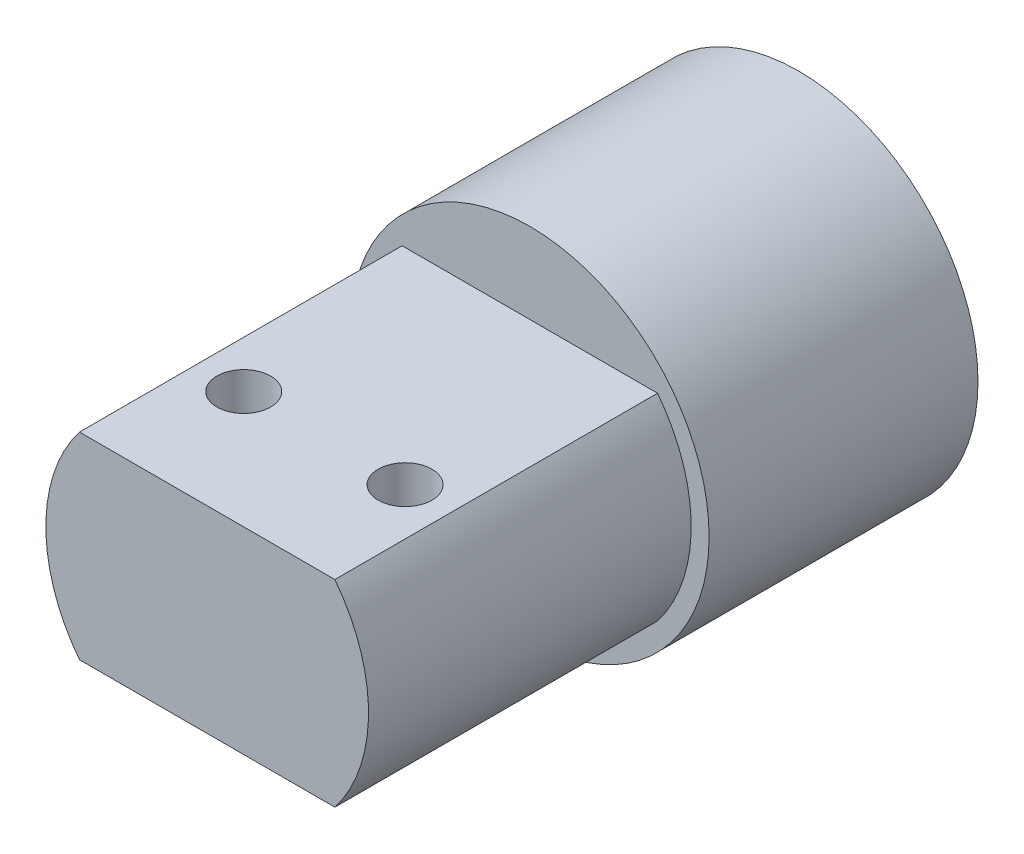
SolidWorks part; units mm, degrees
ref_plane "前视基准面" through (0, 0, 0) normal (0, 0, 1) x (1, 0, 0)
ref_plane "上视基准面" through (0, 0, 0) normal (0, 1, 0) x (1, 0, 0)
ref_plane "右视基准面" through (0, 0, 0) normal (1, 0, 0) x (0, 0, -1)
sketch "草图1" plane through (0, 0, 0) normal (0, 0, 1) x (1, 0, 0)
  line L0 (-11.4891, -8) -> (11.4891, -8)
  arc A0 (11.4891, -8) -> (-11.4891, -8) centre (0, 0) ccw
  circle A1 centre (0, 0) radius 5.25
  dimension "D1" = 28
  dimension "D3" = 10.5
  dimension "D2" = 8
extrude "凸台-拉伸1" add sketch "草图1" along normal blind 15
sketch "草图2" plane through (0, 0, 15) normal (0, 0, 1) x (1, 0, 0)
  line L0 (-13.4164, 4) -> (13.4164, 4)
  line L1 (-11.4891, -8) -> (11.4891, -8) construction
  arc A0 (11.4891, -8) -> (-11.4891, -8) centre (0, 0) ccw construction
  arc A1 (13.4164, 4) -> (-13.4164, 4) centre (0, 0) ccw
  dimension "D1" = 12
extrude "切除-拉伸1" cut sketch "草图2" against normal blind 10
sketch "草图3" plane through (0, 0, 15) normal (0, 0, 1) x (1, 0, 0)
  line L0 (-13.4164, 4) -> (-3.4004, 4) construction
  line L1 (-13.4164, 4) -> (-3.4004, 4) construction
  line L2 (-7.1239, 5.5) -> (7.1239, 5.5)
  line L3 (-7.1239, -5.5) -> (7.1239, -5.5)
  line L4 (-16.2067, 0) -> (21.8127, 0) construction
  line L6 (-16.2067, 5.5) -> (21.8127, 5.5) construction
  line L7 (-16.2067, -5.5) -> (21.8127, -5.5) construction
  arc A0 (-7.1239, 5.5) -> (-7.1239, -5.5) centre (0, 0) ccw
  arc A1 (7.1239, -5.5) -> (7.1239, 5.5) centre (0, 0) ccw
  dimension "D4" = 18
  dimension "D1" = 1.5
  dimension "D2" = 11
  dimension "D3" = 5.5
extrude "凸台-拉伸2" add sketch "草图3" along normal blind 18
sketch "草图4" plane through (0, 5.5, 0) normal (0, 1, 0) x (1, 0, 0)
  line L0 (0, 10.497) -> (0, -50.4006) construction
  line L1 (7.1239, -33) -> (-7.1239, -33) construction
  circle A0 centre (4.5, -26.46) radius 1.5
  circle A1 centre (-4.5, -26.46) radius 1.5
  dimension "D1" = 3
  dimension "D2" = 4.5
  dimension "D3" = 6.54
extrude "切除-拉伸2" cut sketch "草图4" against normal through all
sketch "草图5" plane through (0, 0, 0) normal (0, 0, -1) x (-1, 0, 0)
  circle A0 centre (0, 0) radius 5.25
  circle A1 centre (0, 0) radius 14
extrude "凸台-拉伸3" add sketch "草图5" against normal blind 15
sketch "草图6" plane through (0, 0, 0) normal (0, 0, -1) x (-1, 0, 0)
  circle A0 centre (0, 0) radius 10
  circle A1 centre (0, 0) radius 18.0436
  dimension "D1" = 20
extrude "切除-拉伸3" cut sketch "草图6" against normal blind 15
sketch "草图7" plane through (0, 0, 0) normal (0, 0, -1) x (-1, 0, 0)
  line L0 (1.4402, 4.7881) -> (4.9998, -0.0419)
  line L2 (4.9998, -0.0419) -> (1.4402, 4.7881) construction
  arc A0 (1.4402, 4.7881) -> (4.9998, -0.0419) centre (0, 0) ccw
  circle A1 centre (0, 0) radius 6.9865
  dimension "D1" = 10
  dimension "D2" = 0
extrude "凸台-拉伸4" add sketch "草图7" against normal blind 15
sketch "草图8" plane through (-3.22, 2.3731, 0) normal (0.805, -0.5933, 0) x (0.5933, 0.805, 0)
  circle A0 centre (0, 7.5443) radius 1.35
  dimension "D1" = 2.7
extrude "切除-拉伸4" cut sketch "草图8" against normal blind 15
